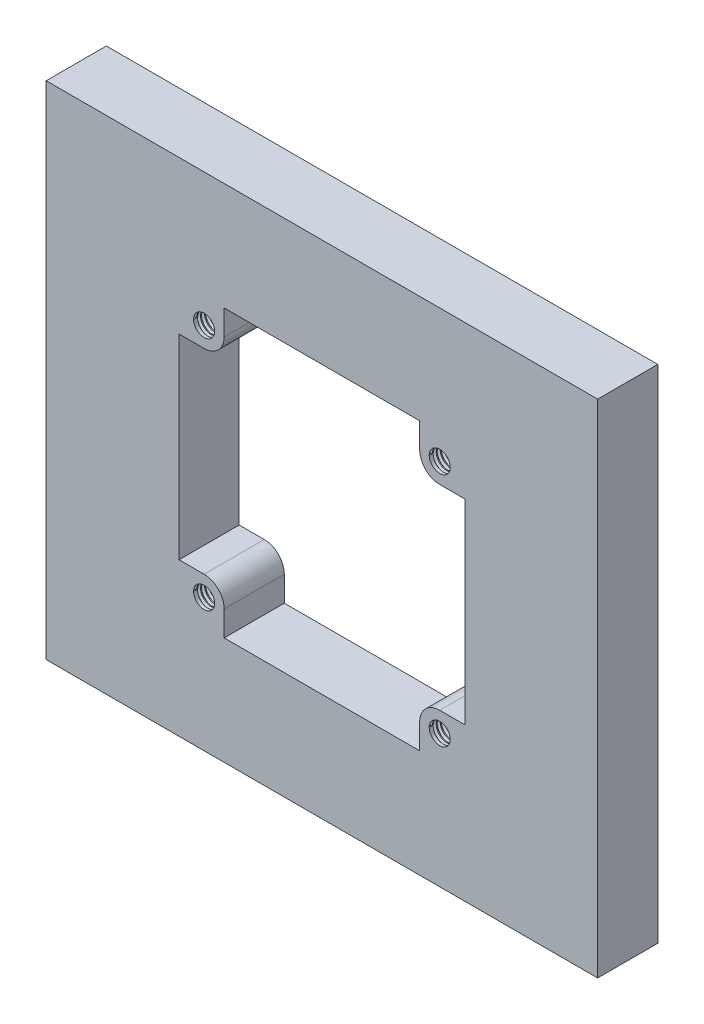
SolidWorks part; units mm, degrees
ref_plane "Ebene vorne" through (0, 0, 0) normal (0, 0, 1) x (1, 0, 0)
ref_plane "Ebene oben" through (0, 0, 0) normal (0, 1, 0) x (1, 0, 0)
ref_plane "Ebene rechts" through (0, 0, 0) normal (1, 0, 0) x (0, 0, -1)
sketch "Skizze1" plane through (0, 0, 0) normal (0, 0, 1) x (1, 0, 0)
  line L0 (0, 0) -> (110, 0)
  line L1 (110, 0) -> (110, 100)
  line L2 (110, 100) -> (0, 100)
  line L3 (0, 100) -> (0, 0)
  dimension "D1" = 110
  dimension "D2" = 100
extrude "Aufsatz-Linear austragen1" add sketch "Skizze1" along normal blind 12
ref_plane "Ebene1" through (55, 0, 0) normal (1, 0, 0) x (0, 0, -1)
ref_plane "Ebene2" through (0, 50, 0) normal (0, 1, 0) x (1, 0, 0)
hole_wizard "M5 Gewindebohrung1" positions "Skizze6" profile "Skizze7" tap size "M5" standard "DIN"
sketch "Skizze6" plane through (0, 0, 0) normal (0, -1, 0) x (-1, 0, 0)
  line L0 (-55, 0) -> (-55, -20.0959) construction
  line L1 (0, 0) -> (-110, 0) construction
  line L3 (-110, -6) -> (3.7683, -6) construction
  line L4 (-110, -12) -> (-110, 0) construction
  point P14 (-95, -6)
  point P16 (-15, -6)
  dimension "D1" = 80
sketch "Skizze7" plane through (15, 0, 6) normal (1, 0, 0) x (0, 0, -1)
  line L0 (0, 0) -> (0, 14)
  line L1 (0, 14) -> (2.1, 12.7382)
  line L2 (2.1, 12.7382) -> (2.1, 0.425)
  line L3 (2.1, 0.425) -> (2.525, 0)
  line L5 (2.525, 0) -> (0, 0)
  line L6 (-2.1, 0.425) -> (-2.525, 0) construction
  line L10 (0, 14) -> (-2.1, 12.7382) construction
  line L11 (0, -6.35) -> (0, 107.95) construction
  dimension "Bohrerdurchmesser" = 4.2
  dimension "Bohrungstiefe" = 14
  dimension "Senkdurchmesser (Oben)" = 5.05
  dimension "Senkwinkel (Oben)" = 90
  dimension "Spitzenwinkel" = 118
cosmetic thread "Bohrungsgewinde1" parameters "D1"=10, "D2"=5
cosmetic thread "Bohrungsgewinde2" parameters "D1"=10, "D2"=5
sketch "Skizze8" plane through (0, 0, 0) normal (0, 0, -1) x (-1, 0, 0)
  line L0 (-55, 101.5707) -> (-55, -13.7402) construction
  line L1 (-115.8696, 50) -> (5.8696, 50) construction
  line L7 (-74.5, 73.5) -> (-74.5, 78.5)
  line L9 (-78.5, 26.5) -> (-31.5, 26.5) construction
  line L10 (-78.5, 26.5) -> (-78.5, 73.5) construction
  line L11 (0, 0) -> (-110, 0) construction
  line L12 (0, 100) -> (0, 0) construction
  line L28 (-78.5, 73.5) -> (-31.5, 73.5) construction
  line L29 (-31.5, 26.5) -> (-31.5, 73.5) construction
  line L30 (-78.5, 26.5) -> (-31.5, 73.5) construction
  line L31 (-75.6716, 70.6716) -> (-31.5, 26.5) construction
  line L32 (-74.5, 21.5) -> (-35.5, 21.5)
  line L33 (-83.5, 30.5) -> (-83.5, 69.5)
  line L34 (-74.5, 78.5) -> (-35.5, 78.5)
  line L35 (-26.5, 30.5) -> (-26.5, 69.5)
  line L36 (-78.5, 26.5) -> (-26.5, 78.5) construction
  line L37 (-75.6716, 70.6716) -> (-31.5, 26.5) construction
  line L38 (-78.5, 69.5) -> (-83.5, 69.5)
  line L39 (-78.5, 30.5) -> (-83.5, 30.5)
  line L40 (-74.5, 26.5) -> (-74.5, 21.5)
  line L41 (-31.5, 30.5) -> (-26.5, 30.5)
  line L42 (-35.5, 26.5) -> (-35.5, 21.5)
  line L43 (-31.5, 69.5) -> (-26.5, 69.5)
  line L44 (-35.5, 73.5) -> (-35.5, 78.5)
  arc A4 (-78.5, 69.5) -> (-74.5, 73.5) centre (-78.5, 73.5) ccw
  arc A5 (-35.5, 73.5) -> (-31.5, 69.5) centre (-31.5, 73.5) ccw
  arc A6 (-31.5, 30.5) -> (-35.5, 26.5) centre (-31.5, 26.5) ccw
  arc A7 (-74.5, 26.5) -> (-78.5, 30.5) centre (-78.5, 26.5) ccw
  point P4 (-55, 50)
  point P5 (-55, 50)
  point P12 (-55, 50)
  point P19 (-55, 50)
  dimension "D1" = 47
  dimension "D2" = 8
  dimension "D3" = 50
  dimension "D4" = 55
  dimension "D5" = 57
  dimension "D6" = 57
extrude "Schnitt-Linear austragen1" cut sketch "Skizze8" against normal through all
hole_wizard "M5 Gewindebohrung3" positions "Skizze11" profile "Skizze12" tap size "M5" standard "ISO" end condition through all
sketch "Skizze11" plane through (0, 0, 0) normal (0, 0, -1) x (-1, 0, 0)
  point P0 (-31.5, 26.5)
  point P3 (-78.5, 26.5)
  point P6 (-78.5, 73.5)
  point P9 (-31.5, 73.5)
sketch "Skizze12" plane through (31.5, 26.5, 0) normal (1, 0, 0) x (0, 1, 0)
  line L0 (0, 0) -> (0, 12)
  line L1 (0, 12) -> (2.1, 12)
  line L2 (2.1, 12) -> (2.1, 0)
  line L5 (2.1, 0) -> (0, 0)
  line L11 (0, -6.35) -> (0, 107.95) construction
  dimension "Bohrerdurchmesser" = 4.2
  dimension "Bohrungstiefe" = 12
cosmetic thread "Bohrungsgewinde3" parameters "D1"=10, "D2"=5
cosmetic thread "Bohrungsgewinde4" parameters "D1"=10, "D2"=5
cosmetic thread "Bohrungsgewinde5" parameters "D1"=10, "D2"=5
cosmetic thread "Bohrungsgewinde6" parameters "D1"=10, "D2"=5
thread "Gewinde2" pitch 0.8 start angle 0, offset 0, length 12, pitch 0.8, diameter 4.2
ref_plane "Ebene4" through (29.4, 26.5, 12) normal (0, -1, 0) x (-1, 0, 0)
sketch "Gewindeprofil2" plane through (29.4, 26.5, 12) normal (0, -1, 0) x (-1, 0, 0)
  line L0 (0, 0) -> (0, 0.8) construction
  line L1 (0, 0) -> (0.433, 0.25)
  line L2 (0.433, 0.25) -> (0.433, 0.35)
  line L3 (0.433, 0.35) -> (0, 0.6)
  line L4 (0.433, 0.3) -> (0, 0.3) construction
  line L11 (0, 0) -> (0, 0.6)
  point P2 (0, 0)
  dimension "Pitch" = 0.8
  dimension "Profile_Angle" = 60
  dimension "Profile_Land" = 0.1
  dimension "Profile_Height" = 0.433
pattern_linear "Lineares Muster1" count 2 spacing 47 along (0, -1, 0) count 2 spacing 47 along (-1, 0, 0) of "Gewinde2"
